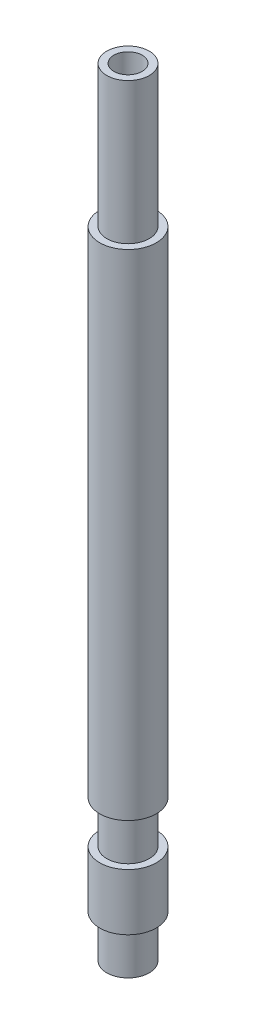
SolidWorks part; units mm, degrees
material "Простая углеродистая сталь"
ref_plane "Спереди" through (0, 0, 0) normal (0, 0, 1) x (1, 0, 0)
ref_plane "Сверху" through (0, 0, 0) normal (0, 1, 0) x (1, 0, 0)
ref_plane "Справа" through (0, 0, 0) normal (1, 0, 0) x (0, 0, -1)
sketch "Эскиз1" plane through (0, 0, 0) normal (0, 1, 0) x (1, 0, 0)
  circle A0 centre (0, 0) radius 2
  circle A1 centre (0, 0) radius 1
  dimension "D1" = 4
  dimension "D2" = 2
extrude "Бобышка-Вытянуть1" add sketch "Эскиз1" along normal blind 55
sketch "Эскиз2" plane through (0, 0, 0) normal (0, 0, 1) x (1, 0, 0)
  line L0 (1.5, 0) -> (2, 0)
  line L1 (1.5, 0) -> (1.5, 3)
  line L2 (2, 0) -> (2, 3)
  line L3 (1.5, 3) -> (2, 3)
  line L4 (0, 0) -> (0, 10.9491) construction
  line L5 (2, 7) -> (1.5, 7)
  line L6 (2, 7) -> (2, 10)
  line L7 (1.5, 7) -> (1.5, 10)
  line L8 (2, 10) -> (1.5, 10)
  line L10 (2, 0) -> (2, 55) construction
  line L11 (2, 55) -> (1.5, 55)
  line L12 (2, 55) -> (2, 45)
  line L13 (1.5, 55) -> (1.5, 45)
  line L14 (2, 45) -> (1.5, 45)
  line L15 (2, 55) -> (-2, 55) construction
  dimension "D1" = 0.5
  dimension "D2" = 3
  dimension "D3" = 3
  dimension "D4" = 0.5
  dimension "D5" = 7
  dimension "D6" = 0.5
  dimension "D7" = 10
revolve "Вырез-Повернуть1" cut sketch "Эскиз2" angle 360 about L4
sketch "Эскиз3" plane through (0, 0, 0) normal (0, 0, 1) x (1, 0, 0)
  line L0 (0, 0) -> (0, 20) construction
  dimension "D1" = 20
